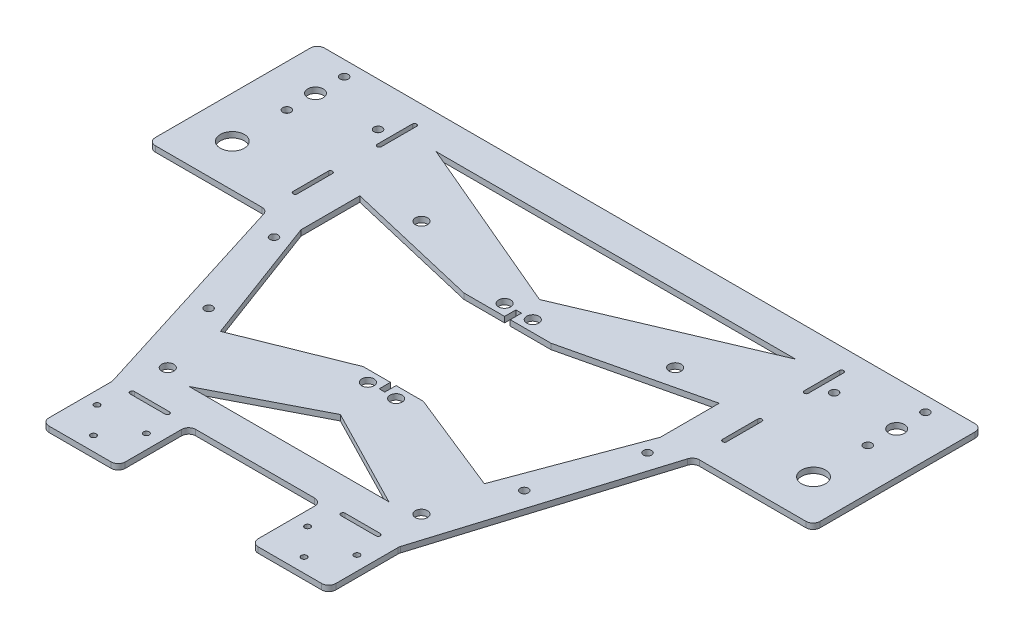
SolidWorks part; units mm, degrees
ref_plane "Front Plane" through (0, 0, 0) normal (0, 0, 1) x (1, 0, 0)
ref_plane "Top Plane" through (0, 0, 0) normal (0, 1, 0) x (1, 0, 0)
ref_plane "Right Plane" through (0, 0, 0) normal (1, 0, 0) x (0, 0, -1)
sketch "Sketch26" plane through (0, 0, 0) normal (0, 1, 0) x (1, 0, 0)
  line L0 (76.0133, 28.8235) -> (76.0133, 88.8235) construction
  line L1 (-63.5382, 76.8235) -> (64.0673, 76.8235)
  line L2 (0.2645, 93.3283) -> (0.2645, -99.0046) construction
  line L3 (21.3527, -51.1765) -> (-20.8236, -51.1765)
  line L4 (76.0133, 88.8235) -> (-76.0328, 88.8235)
  line L5 (-75.4842, 28.8235) -> (-75.4842, 88.8235) construction
  line L6 (115.6892, 88.8235) -> (76.0133, 88.8235)
  line L7 (-77.3206, 28.8235) -> (-115.1602, 28.8235)
  line L8 (-74.935, 27.0713) -> (-50.5239, -50.8121)
  line L9 (75.4699, 27.0594) -> (51.4834, -50.8168)
  line L10 (-117.6602, 31.3235) -> (-117.6602, 86.3235)
  line L11 (-115.1602, 88.8235) -> (-75.4842, 88.8235)
  line L12 (-75.91, 39.1911) -> (-75.91, 51.6911) construction
  line L13 (-76.66, 39.1911) -> (-76.66, 51.6911)
  line L14 (-75.16, 39.1911) -> (-75.16, 51.6911)
  line L15 (-75.4842, 81.0951) -> (-75.4842, 68.5951) construction
  line L16 (-74.7342, 81.0951) -> (-74.7342, 68.5951)
  line L17 (118.1892, 31.3235) -> (118.1892, 86.3235)
  line L18 (-76.2342, 81.0951) -> (-76.2342, 68.5951)
  line L19 (-46.5438, -16.6765) -> (-10.4029, -2.1765)
  line L20 (77.8592, 28.8235) -> (115.6892, 28.8235)
  line L21 (64.0133, 49.7097) -> (64.0133, 28.8235)
  line L22 (64.0133, 28.8235) -> (47.0729, -16.6765)
  line L23 (-63.4842, 28.8235) -> (-46.5438, -16.6765)
  line L24 (47.0729, -16.6765) -> (10.932, -2.1765)
  line L25 (15.7075, 38.3235) -> (64.0133, 49.7097)
  line L26 (-63.4842, 49.7097) -> (-63.4842, 28.8235)
  line L27 (1.2645, 42.3235) -> (1.2645, 38.3235)
  line L28 (1.2645, 42.3235) -> (-0.7355, 42.3235)
  line L29 (1.2645, 38.3235) -> (15.7075, 38.3235)
  line L30 (-0.7355, 42.3235) -> (-0.7355, 38.3235)
  line L31 (64.0673, 76.8235) -> (0.2645, 49.7097)
  line L32 (-0.7355, 38.3235) -> (-15.1784, 38.3235)
  line L33 (76.0133, 81.0951) -> (76.0133, 68.5951) construction
  line L34 (-15.1784, 38.3235) -> (-63.4842, 49.7097)
  line L35 (-63.5382, 76.8235) -> (0.2645, 49.7097)
  line L36 (1.2645, -2.1765) -> (10.932, -2.1765)
  line L37 (75.2633, 81.0951) -> (75.2633, 68.5951)
  line L38 (1.2645, -6.1765) -> (1.2645, -2.1765)
  line L39 (1.2645, -6.1765) -> (-0.7355, -6.1765)
  line L40 (-0.7355, -6.1765) -> (-0.7355, -2.1765)
  line L41 (-0.7355, -2.1765) -> (-10.4029, -2.1765)
  line L42 (-35.1832, -39.1765) -> (35.7123, -39.1765)
  line L43 (0.2645, -20.9512) -> (35.7123, -39.1765)
  line L44 (0.2645, -20.9512) -> (-35.1832, -39.1765)
  line L45 (51.3727, -51.5527) -> (51.3727, -73.6765)
  line L46 (48.8727, -76.1765) -> (26.3527, -76.1765)
  line L47 (76.7633, 81.0951) -> (76.7633, 68.5951)
  line L48 (76.4391, 39.1911) -> (76.4391, 51.6911) construction
  line L49 (77.1891, 39.1911) -> (77.1891, 51.6911)
  line L50 (75.6891, 39.1911) -> (75.6891, 51.6911)
  line L51 (23.8527, -73.6765) -> (23.8527, -53.6765)
  line L52 (37.6127, -76.1765) -> (37.6127, -51.1765) construction
  line L53 (51.3727, -76.1765) -> (51.3727, -51.1765)
  line L54 (23.8527, -51.1765) -> (23.8527, -76.1765)
  line L55 (-50.4095, -51.5599) -> (-50.4095, -73.6765)
  line L56 (-47.9095, -76.1765) -> (-25.8236, -76.1765)
  line L57 (-23.3236, -73.6765) -> (-23.3236, -53.6765)
  line L58 (31.4072, -51.1727) -> (43.9072, -51.1727) construction
  line L59 (31.4072, -50.4227) -> (43.9072, -50.4227)
  line L60 (31.4072, -51.9227) -> (43.9072, -51.9227)
  line L61 (-30.8781, -51.1727) -> (-43.3781, -51.1727) construction
  line L62 (-30.8781, -50.4227) -> (-43.3781, -50.4227)
  line L63 (-30.8781, -51.9227) -> (-43.3781, -51.9227)
  circle A0 centre (45.2645, 52.8235) radius 2.15
  circle A1 centre (45.2645, -37.1765) radius 2.15
  circle A2 centre (5.2645, 42.3235) radius 2.15
  circle A3 centre (5.2645, -6.1765) radius 2.15
  circle A4 centre (103.3673, 43.8235) radius 4.25
  arc A5 (118.1892, 31.3235) -> (115.6892, 28.8235) centre (115.6892, 31.3235) cw
  circle A6 centre (103.3673, 73.3235) radius 2.75
  circle A7 centre (103.3673, 83.5235) radius 1.45
  circle A8 centre (103.3133, 63.1237) radius 1.45
  circle A9 centre (81.1673, 73.3235) radius 1.45
  arc A10 (118.1892, 86.3235) -> (115.6892, 88.8235) centre (115.6892, 86.3235) ccw
  arc A11 (-117.6602, 86.3235) -> (-115.1602, 88.8235) centre (-115.1602, 86.3235) cw
  circle A12 centre (-80.6382, 73.3235) radius 1.45
  circle A13 centre (-102.7842, 63.1237) radius 1.45
  circle A14 centre (-102.8382, 83.5235) radius 1.45
  circle A15 centre (-102.8382, 73.3235) radius 2.75
  arc A16 (-117.6602, 31.3235) -> (-115.1602, 28.8235) centre (-115.1602, 31.3235) ccw
  arc A17 (75.2633, 81.0951) -> (76.7633, 81.0951) centre (76.0133, 81.0951) cw
  circle A18 centre (-102.8382, 43.8235) radius 4.25
  circle A19 centre (-4.7355, -6.1765) radius 2.15
  arc A20 (76.7633, 68.5951) -> (75.2633, 68.5951) centre (76.0133, 68.5951) cw
  arc A21 (77.1891, 39.1911) -> (75.6891, 39.1911) centre (76.4391, 39.1911) cw
  arc A22 (75.6891, 51.6911) -> (77.1891, 51.6911) centre (76.4391, 51.6911) cw
  circle A23 centre (-4.7355, 42.3235) radius 2.15
  circle A24 centre (-44.7355, -37.1765) radius 2.15
  circle A25 centre (-44.7355, 52.8235) radius 2.15
  arc A26 (-76.66, 39.1911) -> (-75.16, 39.1911) centre (-75.91, 39.1911) ccw
  arc A27 (-75.16, 51.6911) -> (-76.66, 51.6911) centre (-75.91, 51.6911) ccw
  arc A28 (-74.7342, 81.0951) -> (-76.2342, 81.0951) centre (-75.4842, 81.0951) ccw
  arc A29 (-76.2342, 68.5951) -> (-74.7342, 68.5951) centre (-75.4842, 68.5951) ccw
  circle A30 centre (28.8527, -61.1765) radius 1
  circle A31 centre (37.6127, -71.1765) radius 1
  circle A32 centre (46.3727, -61.1765) radius 1
  circle A33 centre (28.8527, -61.1765) radius 1
  circle A34 centre (46.3727, -61.1765) radius 1
  circle A35 centre (-28.3236, -61.1765) radius 1
  circle A36 centre (-45.8436, -61.1765) radius 1
  circle A37 centre (-37.0836, -71.1765) radius 1
  arc A38 (31.4072, -50.4227) -> (31.4072, -51.9227) centre (31.4072, -51.1727) ccw
  arc A39 (43.9072, -51.9227) -> (43.9072, -50.4227) centre (43.9072, -51.1727) ccw
  arc A40 (-30.8781, -50.4227) -> (-30.8781, -51.9227) centre (-30.8781, -51.1727) cw
  arc A41 (-43.3781, -51.9227) -> (-43.3781, -50.4227) centre (-43.3781, -51.1727) cw
  arc A42 (77.8592, 28.8235) -> (75.4699, 27.0594) centre (77.8592, 26.3235) ccw
  arc A43 (-74.935, 27.0713) -> (-77.3206, 28.8235) centre (-77.3206, 26.3235) ccw
  arc A44 (51.3727, -51.5527) -> (51.4834, -50.8168) centre (53.8727, -51.5527) cw
  arc A45 (21.3527, -51.1765) -> (23.8527, -53.6765) centre (21.3527, -53.6765) cw
  arc A46 (-20.8236, -51.1765) -> (-23.3236, -53.6765) centre (-20.8236, -53.6765) ccw
  arc A47 (-50.4095, -51.5599) -> (-50.5239, -50.8121) centre (-52.9095, -51.5599) ccw
  arc A48 (-23.3236, -73.6765) -> (-25.8236, -76.1765) centre (-25.8236, -73.6765) cw
  arc A49 (-47.9095, -76.1765) -> (-50.4095, -73.6765) centre (-47.9095, -73.6765) cw
  circle A50 centre (66.5151, 21.7665) radius 1.45
  circle A51 centre (56.2618, -11.698) radius 1.45
  circle A52 centre (-55.7328, -11.698) radius 1.45
  circle A53 centre (-65.9861, 21.7665) radius 1.45
  arc A54 (48.8727, -76.1765) -> (51.3727, -73.6765) centre (48.8727, -73.6765) ccw
  arc A55 (26.3527, -76.1765) -> (23.8527, -73.6765) centre (26.3527, -73.6765) cw
  circle A56 centre (0.2645, 7.8235) radius 1.4516
  point P60 (-75.91, 45.4411)
  point P63 (76.0133, 74.8451)
  point P71 (76.4391, 45.4411)
  point P77 (-75.4842, 74.8451)
  point P99 (0.2645, 42.3235)
  point P107 (0.2645, -6.1765)
  point P112 (0.2645, -39.1765)
  point P136 (37.6572, -51.1727)
  point P143 (-37.1281, -51.1727)
  point P162 (-23.3236, -51.1765)
  point P167 (-23.3236, -76.1765)
  dimension "D6" = 4.3
  dimension "D13" = 8.5
  dimension "D14" = 2.9
  dimension "D15" = 2.9
  dimension "D16" = 2.9
  dimension "D10" = 2.5
  dimension "D21" = 2.5
  dimension "D3" = 45
  dimension "D7" = 4.3
  dimension "D8" = 5.5
  dimension "D22" = 45
  dimension "D4" = 48.5
  dimension "D11" = 4.3
  dimension "D24" = 4.3
  dimension "D28" = 5
  dimension "D36" = 20
  dimension "D37" = 2.5
  dimension "D38" = 2.9
  dimension "D41" = 2.9
  dimension "D40" = 2.5
  dimension "D5" = 90
  dimension "D12" = 15
  dimension "D17" = 10.2
  dimension "D18" = 10.2
  dimension "D19" = 22.2
  dimension "D20" = 29.5
  dimension "D9" = 40
  dimension "D23" = 40
  dimension "D25" = 36
  dimension "D26" = 45
  dimension "D27" = 12
  dimension "D29" = 12
  dimension "D30" = 12
  dimension "D31" = 1
  dimension "D32" = 4
  dimension "D33" = 27.52
  dimension "D34" = 25
  dimension "D35" = 10
  dimension "D39" = 7
  dimension "D42" = 35
  dimension "D43" = 14
  dimension "D44" = 4
  dimension "D45" = 4
  dimension "D46" = 4
extrude "Boss-Extrude4" add sketch "Sketch26" along normal blind 2 contours L20 A5 L17 A10 A20 region at (0.2645, 0, 48.2981)
